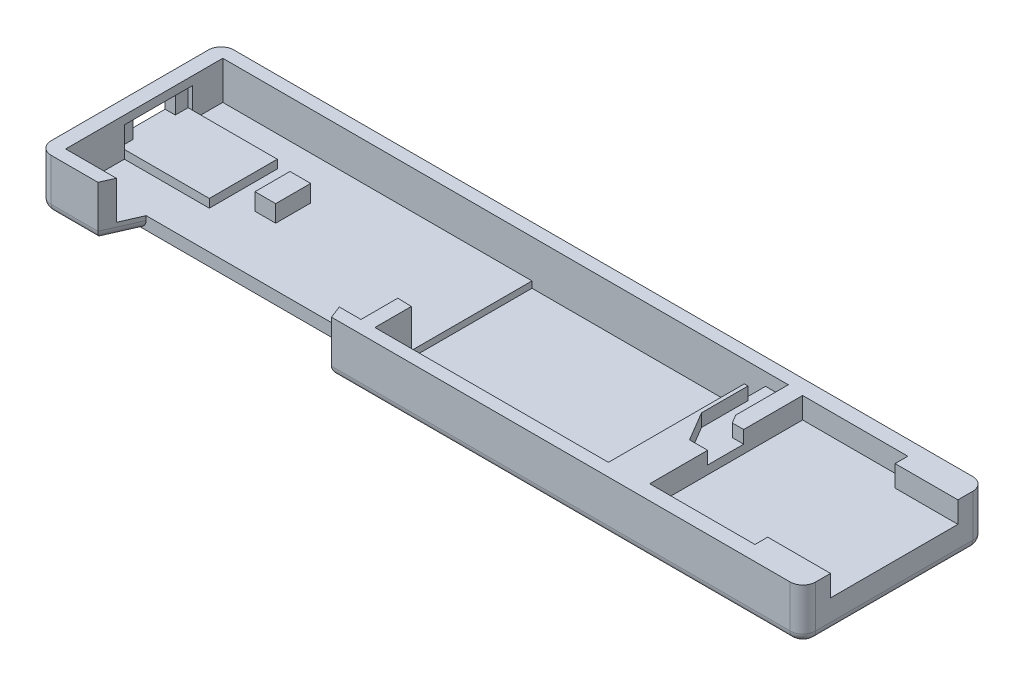
SolidWorks part; units mm, degrees
ref_plane "前视基准面" through (0, 0, 0) normal (0, 0, 1) x (1, 0, 0)
ref_plane "上视基准面" through (0, 0, 0) normal (0, 1, 0) x (1, 0, 0)
ref_plane "右视基准面" through (0, 0, 0) normal (1, 0, 0) x (0, 0, -1)
sketch "草图3" plane through (0, 0, 0) normal (0, 1, 0) x (1, 0, 0)
  line L1 (-39.9314, 29.2531) -> (140.0686, 29.2531)
  line L2 (-39.9314, 29.2531) -> (-39.9314, -13.7469)
  line L3 (-39.9314, -13.7469) -> (140.0686, -13.7469)
  line L4 (140.0686, 29.2531) -> (140.0686, -13.7469)
extrude "凸台-拉伸1" add sketch "草图3" along normal blind 12
sketch "草图4" plane through (0, 0, 0) normal (0, 1, 0) x (1, 0, 0)
  line L0 (-22.4696, -5.8589) -> (26.0023, -5.8589)
  line L1 (-39.9314, -13.7469) -> (140.0686, -13.7469) construction
  line L2 (-25.9314, -13.7469) -> (29.0686, -13.7469)
  line L5 (-25.9314, -13.7469) -> (-22.4696, -5.8589)
  line L6 (29.0686, -13.7469) -> (26.0023, -5.8589)
  point P11 (-22.4696, -5.8589)
  point P12 (26.0023, -5.8589)
extrude "切除-拉伸1" cut sketch "草图4" along normal blind 52
sketch "草图5" plane through (0, 12, 0) normal (0, 1, 0) x (1, 0, 0)
  line L6 (140.0686, -13.7469) -> (140.0686, 29.2531) construction
  line L7 (140.0686, 7.7531) -> (140.0686, 22.7531)
  line L8 (140.0686, 7.7531) -> (140.0686, -7.2469)
  line L9 (140.0686, 22.7531) -> (125.2765, 22.7531)
  line L10 (125.2765, 22.7531) -> (125.2765, -7.2469)
  line L11 (125.2765, -7.2469) -> (140.0686, -7.2469)
  point P0 (140.0686, 7.7531)
extrude "切除-拉伸2" cut sketch "草图5" against normal blind 5
sketch "草图7" plane through (0, 12, 0) normal (0, 1, 0) x (1, 0, 0)
  line L0 (125.2765, 22.7531) -> (125.2765, -7.2469) construction
  line L1 (125.2765, 7.7531) -> (125.2765, 25.7531)
  line L2 (125.2765, 7.7531) -> (125.2765, -10.2469)
  line L3 (125.2765, -10.2469) -> (100.5008, -10.2469)
  line L4 (100.5008, -10.2469) -> (100.5008, 25.7531)
  line L5 (100.5008, 25.7531) -> (125.2765, 25.7531)
  point P0 (125.2765, 7.7531)
extrude "切除-拉伸3" cut sketch "草图7" against normal blind 5
sketch "草图8" plane through (0, 12, 0) normal (0, 1, 0) x (1, 0, 0)
  line L1 (36.2763, 26.2531) -> (91.2763, 26.2531)
  line L2 (36.2763, 26.2531) -> (36.2763, -10.7469)
  line L3 (36.2763, -10.7469) -> (91.2763, -10.7469)
  line L4 (91.2763, 26.2531) -> (91.2763, -10.7469)
  line L6 (140.0686, 29.2531) -> (-39.9314, 29.2531) construction
  line L7 (29.0686, -13.7469) -> (140.0686, -13.7469) construction
  dimension "D1" = 3
  dimension "D2" = 3
extrude "切除-拉伸4" cut sketch "草图8" against normal blind 10.5
sketch "草图9" plane through (0, 12, 0) normal (0, 1, 0) x (1, 0, 0)
  line L0 (91.2763, -10.7469) -> (91.2763, 26.2531) construction
  line L1 (91.2763, 26.2531) -> (96.6358, 26.2531)
  line L2 (91.2763, 26.2531) -> (91.2763, 21.2551)
  line L4 (96.6358, 26.2531) -> (96.6358, 22.1306)
  line L5 (100.5008, 25.7531) -> (100.5008, -10.2469) construction
  line L7 (92.1327, 21.2551) -> (92.1327, 10.3104)
  line L12 (96.2367, 3.394) -> (100.5008, 3.394)
  line L13 (100.5008, 11.8772) -> (100.5008, 3.394)
  line L14 (92.1327, 10.3104) -> (96.2367, 3.394)
  line L15 (96.6358, 13.8621) -> (97.8136, 11.8772)
  line L17 (97.8136, 11.8772) -> (100.5008, 11.8772)
  line L19 (96.6358, 13.8621) -> (96.6358, 22.1306)
  line L20 (92.1327, 21.2551) -> (91.2763, 21.2551)
extrude "切除-拉伸5" cut sketch "草图9" against normal blind 3
sketch "草图10" plane through (0, 12, 0) normal (0, 1, 0) x (1, 0, 0)
  line L4 (-29.1302, -10.7469) -> (32.9986, -10.7469)
  line L5 (-29.1302, -10.7469) -> (-29.1302, -2.0631)
  line L6 (-29.1302, -2.0631) -> (32.9986, -2.0631)
  line L7 (32.9986, -10.7469) -> (32.9986, -2.0631)
extrude "切除-拉伸6" cut sketch "草图10" against normal blind 8
sketch "草图11" plane through (0, 12, 0) normal (0, 1, 0) x (1, 0, 0)
  line L0 (32.9986, -10.7469) -> (-36.5397, -10.7469)
  line L1 (36.2763, 26.2531) -> (36.2763, -10.7469) construction
  line L5 (-36.5397, 26.2531) -> (-36.5397, -10.7469)
  line L9 (36.2763, 26.2531) -> (36.2763, -2.1672)
  line L10 (-36.5397, 26.2531) -> (36.2763, 26.2531)
  line L11 (32.9986, -10.7469) -> (32.9986, -2.0631)
  line L12 (32.9986, -10.7469) -> (32.9986, -2.0631) construction
  line L13 (32.9986, -2.0631) -> (36.2763, -2.1672)
extrude "切除-拉伸8" cut sketch "草图11" against normal blind 9
fillet "圆角2" radius 2 7 edges at (140.0686, 0, -7.7531) (84.5686, 0, 13.7469) (27.5354, 0, 9.8029) (-24.2005, 0, 9.8029) (-32.9314, 0, 13.7469) (-39.9314, 0, -7.7531) (50.0686, 0, -29.2531)
fillet "圆角3" radius 3 8 edges at (-39.3456, 0.5858, -28.6673) (-39.3456, 0.5858, 13.1611) (139.4828, 0.5858, 13.1611) (139.4828, 0.5858, -28.6673) (140.0686, 7, -29.2531) (140.0686, 7, 13.7469) (-39.9314, 7, 13.7469) (-39.9314, 7, -29.2531)
sketch "草图12" plane through (0, 3, 0) normal (0, 1, 0) x (1, 0, 0)
  line L0 (-36.5397, 26.2531) -> (-36.5397, -10.7469) construction
  line L1 (-36.5397, 19.0821) -> (-16.5397, 19.0821)
  line L2 (-36.5397, 19.0821) -> (-36.5397, 3.0821)
  line L3 (-36.5397, 3.0821) -> (-16.5397, 3.0821)
  line L4 (-16.5397, 19.0821) -> (-16.5397, 3.0821)
extrude "凸台-拉伸2" add sketch "草图12" along normal blind 2
sketch "草图13" plane through (-36.5397, 0, 0) normal (1, 0, 0) x (0, 0, -1)
  line L1 (3.0821, 5) -> (19.0821, 5)
  line L2 (3.0821, 5) -> (3.0821, 10)
  line L3 (3.0821, 10) -> (19.0821, 10)
  line L4 (19.0821, 5) -> (19.0821, 10)
  point P5 (18.0821, 5)
extrude "切除-拉伸9" cut sketch "草图13" against normal blind 1
sketch "草图14" plane through (-37.5397, 0, 0) normal (1, 0, 0) x (0, 0, -1)
  line L1 (3.0821, 5) -> (19.0821, 5) construction
  line L4 (16.0821, 5) -> (6.0821, 5)
  line L5 (16.0821, 5) -> (16.0821, 9.5)
  line L6 (16.0821, 9.5) -> (6.0821, 9.5)
  line L7 (6.0821, 5) -> (6.0821, 9.5)
  point P10 (0, 0)
extrude "切除-拉伸10" cut sketch "草图14" against normal blind 11
sketch "草图15" plane through (0, 5, 0) normal (0, 1, 0) x (1, 0, 0)
  line L2 (-10.5397, 16.0821) -> (-5.6617, 16.0821)
  line L3 (-10.5397, 16.0821) -> (-10.5397, 7.8336)
  line L4 (-10.5397, 7.8336) -> (-5.6617, 7.8336)
  line L5 (-5.6617, 16.0821) -> (-5.6617, 7.8336)
extrude "凸台-拉伸3" add sketch "草图15" along normal blind 2 and the other way blind 3
